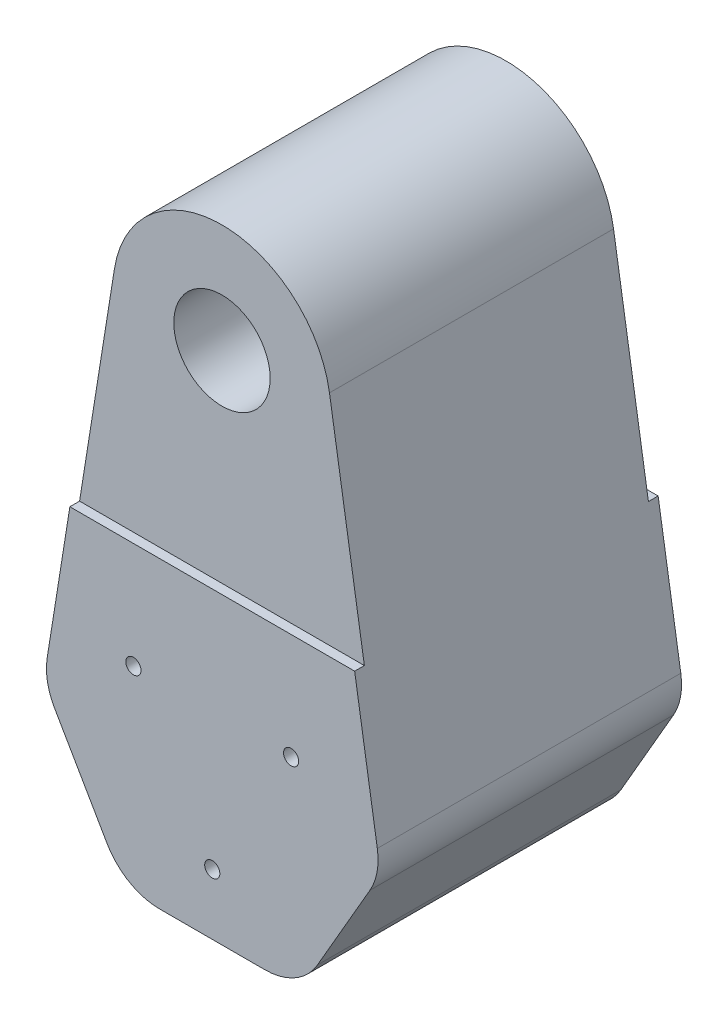
SolidWorks part; units mm, degrees
material "6061-T6 (SS)"
ref_plane "Front Plane" through (0, 0, 0) normal (0, 0, 1) x (1, 0, 0)
ref_plane "Top Plane" through (0, 0, 0) normal (0, 1, 0) x (1, 0, 0)
ref_plane "Right Plane" through (0, 0, 0) normal (1, 0, 0) x (0, 0, -1)
sketch "Sketch1" plane through (0, 0, 0) normal (0, 0, 1) x (1, 0, 0)
  line L0 (-17.7137, 2.8246) -> (-27.1957, -56.6385)
  line L1 (-25.9808, -63.2132) -> (-17.3205, -78.2132)
  line L2 (-8.6603, -83.2132) -> (8.6603, -83.2132)
  line L3 (17.3205, -78.2132) -> (25.9808, -63.2132)
  line L4 (27.1957, -56.6385) -> (17.7137, 2.8246)
  line L11 (105.7091, -33.2132) -> (-105.7091, -33.2132) construction
  line L12 (-93.4741, -83.2132) -> (93.4741, -83.2132) construction
  line L13 (0, -58.2132) -> (21.6506, -70.7132) construction
  line L14 (-23.4603, -33.2132) -> (23.4603, -33.2132)
  circle A0 centre (0, 0) radius 7.9375
  arc A1 (-17.7137, 2.8246) -> (17.7137, 2.8246) centre (0, 0) cw
  circle A2 centre (0, -58.2132) radius 15 construction
  circle A3 centre (-12.9904, -50.7132) radius 1.25
  circle A4 centre (12.9904, -50.7132) radius 1.25
  circle A5 centre (0, -73.2132) radius 1.25
  arc A8 (25.9808, -63.2132) -> (27.1957, -56.6385) centre (17.3205, -58.2132) ccw
  arc A9 (8.6603, -83.2132) -> (17.3205, -78.2132) centre (8.6603, -73.2132) ccw
  arc A10 (-17.3205, -78.2132) -> (-8.6603, -83.2132) centre (-8.6603, -73.2132) ccw
  arc A11 (-27.1957, -56.6385) -> (-25.9808, -63.2132) centre (-17.3205, -58.2132) ccw
  circle A12 centre (0, -58.2132) radius 15 construction
  circle A13 centre (-12.9904, -50.7132) radius 1.65 construction
  point P11 (0, -83.2132)
  point P20 (0, -58.2132)
  dimension "D1" = 15.875
  dimension "D4" = 2.5
  dimension "D8" = 10
  dimension "D11" = 10
  dimension "D3" = 3
extrude "Boss-Extrude1" add sketch "Sketch1" along normal mid plane 50 contours L0 A11 L1 A10 L2 A9 L3 A8 L4 L14 A3 A4 A5 region at (0, -56.6086, 0)
extrude "Boss-Extrude2" add sketch "Sketch1<3>" along normal mid plane 46.7996 contours A1 L0 L14 L4 A0 region at (0, -11.8814, 0)
sketch "Sketch1<3>" plane through (0, 0, 0) normal (0, 0, 1) x (1, 0, 0) same geometry as "Sketch1"
